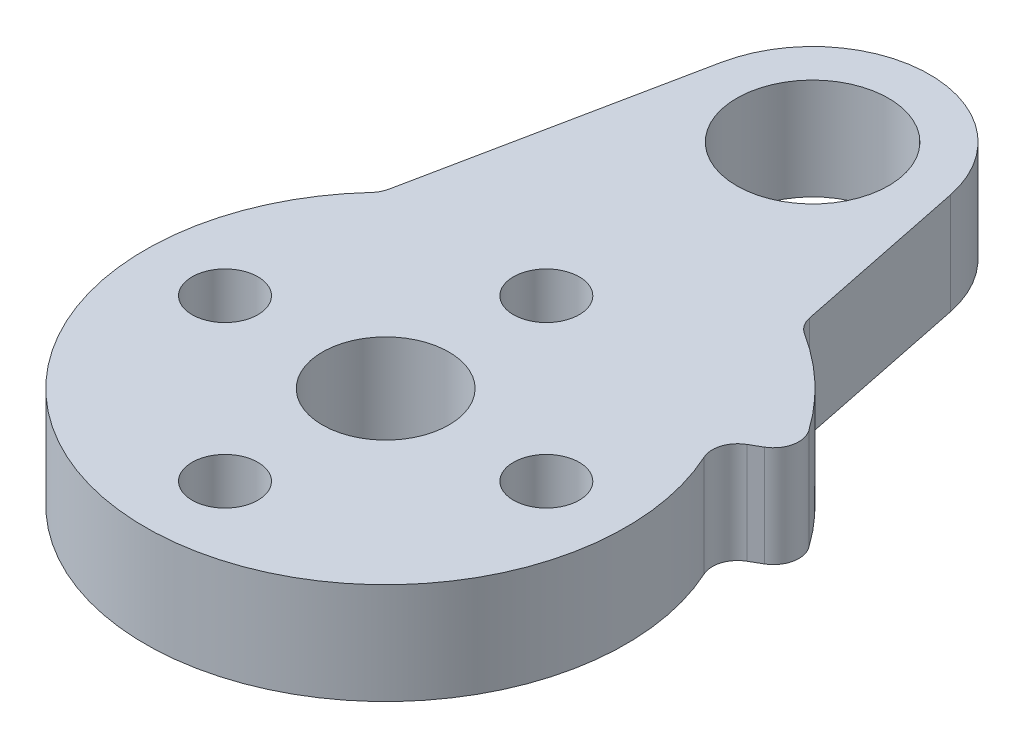
SolidWorks part; units mm, degrees
ref_plane "Front Plane" through (0, 0, 0) normal (0, 0, 1) x (1, 0, 0)
ref_plane "Top Plane" through (0, 0, 0) normal (0, 1, 0) x (1, 0, 0)
ref_plane "Right Plane" through (0, 0, 0) normal (1, 0, 0) x (0, 0, -1)
sketch "Sketch1" plane through (0, 0, 0) normal (0, 1, 0) x (1, 0, 0)
  line L1 (-4.5316, 17.7996) -> (-7.8384, 1.6)
  line L2 (4.5316, 17.7996) -> (7.8384, 1.6)
  arc A0 (-7.8384, 1.6) -> (7.8384, 1.6) centre (0, 0) ccw
  arc A1 (4.5316, 17.7996) -> (-4.5316, 17.7996) centre (0, 16.8746) ccw
  circle A2 centre (0, 16.8746) radius 3
  circle A3 centre (0, 0) radius 2.5
extrude "Boss-Extrude1" add sketch "Sketch1" along normal blind 4
sketch "Sketch2" plane through (0, 4, 0) normal (0, 1, 0) x (1, 0, 0)
  line L0 (0, 0) -> (0, 6.35) construction
  circle A0 centre (0, 6.35) radius 1.3
  circle A1 centre (6.35, 0) radius 1.3
  circle A2 centre (0, -6.35) radius 1.3
  circle A3 centre (-6.35, 0) radius 1.3
  point P13 (0, 0)
  dimension "D1" = 4
extrude "Cut-Extrude1" cut sketch "Sketch2" against normal blind 4
sketch "Sketch3" plane through (0, 4, 0) normal (0, 1, 0) x (1, 0, 0)
  line L0 (-7.8384, 1.6) -> (-6.8137, 6.62)
  line L1 (6.8137, 6.62) -> (7.8384, 1.6)
  line L2 (7.8384, 1.6) -> (4.5316, 17.7996) construction
  arc A1 (-6.8137, 6.62) -> (6.8137, 6.62) centre (0, 0) ccw
  arc A2 (-7.8384, 1.6) -> (7.8384, 1.6) centre (0, 0) ccw construction
  arc A3 (-7.8384, 1.6) -> (7.8384, 1.6) centre (0, 0) ccw
extrude "Boss-Extrude2" add sketch "Sketch3" against normal blind 4
sketch "Sketch4" plane through (0, 4, 0) normal (0, 1, 0) x (1, 0, 0)
  line L1 (8.2272, 4.75) -> (10.3923, 6)
  line L2 (0, 12) -> (0, 9.5)
  arc A0 (10.3923, 6) -> (0, 12) centre (0, 0) ccw
  arc A1 (8.2272, 4.75) -> (0, 9.5) centre (0, 0) ccw
extrude "Boss-Extrude3" add sketch "Sketch4" against normal up to surface (4 mm away) up to face at (0, 0, -9.1048)
fillet "Fillet1" radius 1 4 edges at (6.0495, 2, -10.3636) (8.2272, 2, -4.75) (10.3923, 2, -6) (-6.8137, 2, -6.62)
